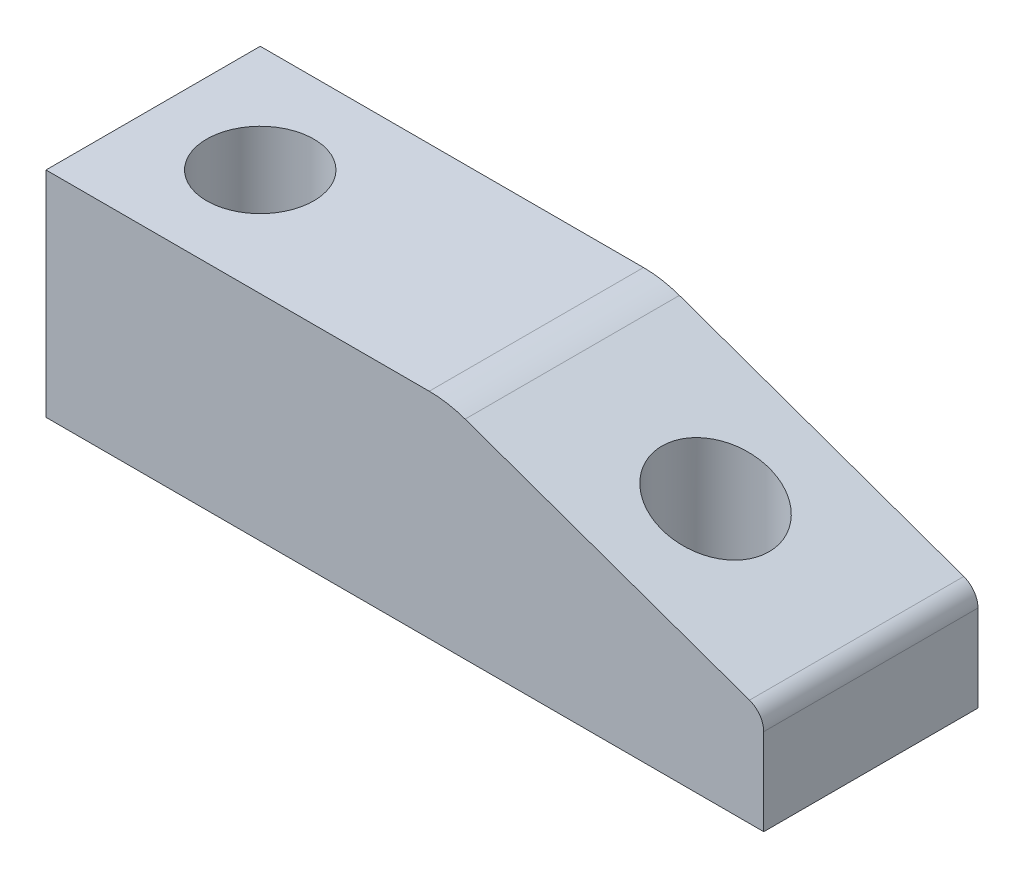
SolidWorks part; units mm, degrees
ref_plane "Front Plane" through (0, 0, 0) normal (0, 0, 1) x (1, 0, 0)
ref_plane "Top Plane" through (0, 0, 0) normal (0, 1, 0) x (1, 0, 0)
ref_plane "Right Plane" through (0, 0, 0) normal (1, 0, 0) x (0, 0, -1)
sketch "Sketch1" plane through (0, 0, 0) normal (0, 0, 1) x (1, 0, 0)
  line L1 (-67, 20) -> (67, 20)
  line L2 (-67, 20) -> (-67, -20)
  line L3 (-67, -20) -> (67, -20)
  line L4 (67, 20) -> (67, -20)
  line L5 (-67, 20) -> (67, -20) construction
  line L6 (-67, -20) -> (67, 20) construction
  point P0 (0, 0)
  dimension "D1" = 134
  dimension "D2" = 40
extrude "Boss-Extrude1" add sketch "Sketch1" along normal blind 20 and the other way blind 20
sketch "Sketch2" plane through (0, 0, 20) normal (0, 0, 1) x (1, 0, 0)
  line L0 (8, 20) -> (67, -1)
  line L1 (67, 20) -> (-67, 20) construction
  line L2 (67, -20) -> (67, 20) construction
  line L3 (8, 20) -> (67, 20)
  line L4 (67, 20) -> (67, -1)
  line L6 (-67, -20) -> (67, -20) construction
  dimension "D1" = 75
  dimension "D2" = 19
extrude "Cut-Extrude1" cut sketch "Sketch2" against normal up to surface (40 mm away) up to face at (0, 0, -20)
fillet "Fillet1" radius 20 1 edges at (8, 20, 0)
fillet "Fillet2" radius 4 1 edges at (67, -1, 0)
sketch "Sketch3" plane through (0, 20, 0) normal (0, 1, 0) x (1, 0, 0)
  line L0 (-67, 0) -> (67, 0) construction
  line L1 (-67, 20) -> (-67, -20) construction
  line L2 (67, 20) -> (67, -20) construction
  line L3 (4.5468, -20) -> (-67, -20) construction
  circle A0 centre (-47, 0) radius 10
  circle A1 centre (38, 0) radius 10
  dimension "D1" = 20
  dimension "D2" = 20
  dimension "D3" = 20
  dimension "D4" = 29
  dimension "D5" = 20
extrude "Cut-Extrude2" cut sketch "Sketch3" against normal blind 29
sketch "Sketch4" plane through (0, -9, 0) normal (0, 1, 0) x (1, 0, 0)
  circle A0 centre (-47, 0) radius 6
  circle A1 centre (38, 0) radius 6
extrude "Cut-Extrude3" cut sketch "Sketch4" against normal up to surface (11 mm away) up to face at (0, -20, 0)
equation "\"D1@Sketch2\"=75"
